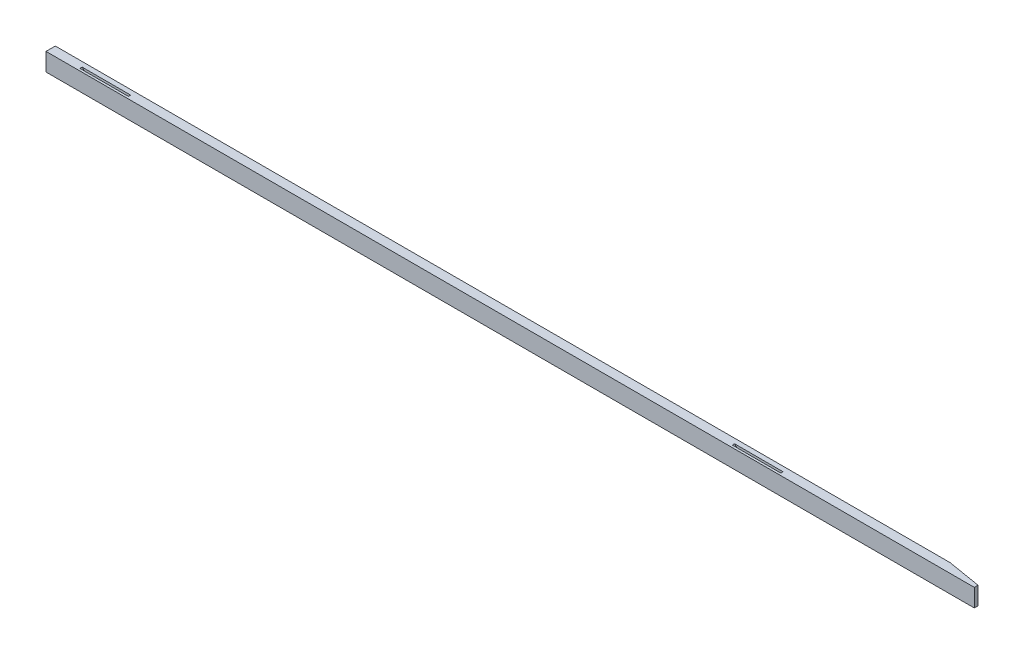
SolidWorks part; units mm, degrees
ref_plane "前视基准面" through (0, 0, 0) normal (0, 0, 1) x (1, 0, 0)
ref_plane "上视基准面" through (0, 0, 0) normal (0, 1, 0) x (1, 0, 0)
ref_plane "右视基准面" through (0, 0, 0) normal (1, 0, 0) x (0, 0, -1)
sketch "草图1" plane through (0, 0, 0) normal (0, 0, 1) x (1, 0, 0)
  line L0 (0, 24) -> (0, -24)
  line L1 (0, -24) -> (2490, -24)
  line L2 (2490, -24) -> (2490, 24)
  line L3 (2490, 24) -> (0, 24)
  point P4 (0, 0)
  dimension "D1" = 2490
  dimension "D2" = 48
extrude "凸台-拉伸1" add sketch "草图1" along normal blind 25
sketch "草图2" plane through (0, 24, 0) normal (0, 1, 0) x (1, 0, 0)
  line L0 (1842.5, -13) -> (1842.5, -19)
  line L1 (1842.5, -19) -> (1957.5, -19)
  line L2 (1957.5, -19) -> (1957.5, -13)
  line L3 (1957.5, -13) -> (1842.5, -13)
  line L4 (2490, -25) -> (0, -25) construction
  line L5 (2490, -25) -> (2490, 0) construction
  point P6 (1900, -13)
  point P9 (1842.5, -13)
  point P10 (1957.5, -13.2698)
  dimension "D1" = 115
  dimension "D2" = 6
  dimension "D3" = 6
  dimension "D4" = 590
extrude "切除-拉伸1" cut sketch "草图2" against normal blind 7.5
draft "拔模1" type of draft neutral plane draft angle 45 faces to draft 2 face at (1957.5, 20.25, 16) face at (1842.5, 20.25, 16) neutral plane through (0, 16.5, 0) neutral plane normal (0, 1, 0) parameters "D1"=45
mirror "镜向1" about plane through (0, 0, 0) normal (0, 1, 0) of face at (1900, 20.25, 19) of face at (1961.25, 20.25, 16) of face at (1900, 20.25, 13) of face at (1838.75, 20.25, 16) of face at (1900, 16.5, 16)
pattern_linear "阵列(线性)1" count 2 spacing 1750 along (-1, 0, 0) of face at (1900, 20.25, 19) of face at (1838.75, 20.25, 16) of face at (1900, 16.5, 16) of face at (1961.25, 20.25, 16) of face at (1900, 20.25, 13) of face at (1838.75, -20.25, 16) of face at (1900, -16.5, 16) of face at (1900, -20.25, 13) of face at (1961.25, -20.25, 16) of face at (1900, -20.25, 19)
sketch "草图3" plane through (0, -24, 0) normal (0, -1, 0) x (1, 0, 0)
  line L5 (2400, 0) -> (2490, 0)
  line L6 (0, 0) -> (2490, 0) construction
  line L7 (2490, 0) -> (2490, 15)
  line L8 (2490, 25) -> (2490, 0) construction
  line L9 (2490, 15) -> (2400, 0)
  dimension "D1" = 90
  dimension "D2" = 10
extrude "切除-拉伸2" cut sketch "草图3" against normal up to next
